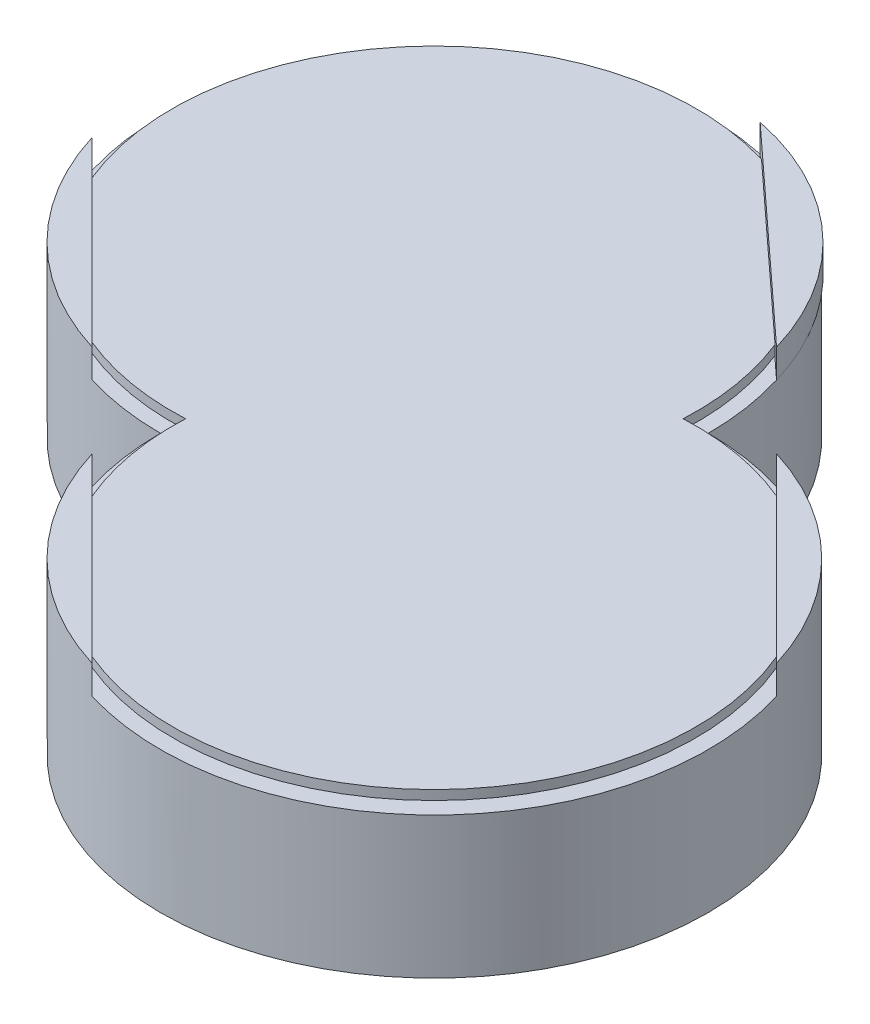
SolidWorks part; units mm, degrees
ref_plane "Front Plane" through (0, 0, 0) normal (0, 0, 1) x (1, 0, 0)
ref_plane "Top Plane" through (0, 0, 0) normal (0, 1, 0) x (1, 0, 0)
ref_plane "Right Plane" through (0, 0, 0) normal (1, 0, 0) x (0, 0, -1)
sketch "Sketch1" plane through (0, 0, 0) normal (0, 1, 0) x (1, 0, 0)
  line L0 (-44.4879, 0) -> (-58.6165, 14.1994)
  line L1 (0, 44.4879) -> (-14.1994, 58.6165)
  arc A0 (-58.6165, 0) -> (0, 58.6165) centre (0, 0) ccw
  arc A1 (0, 58.6165) -> (-58.6165, 0) centre (-58.6165, 58.6165) ccw
  arc A2 (-14.1994, 58.6165) -> (-58.6165, 14.1994) centre (-58.6165, 58.6165) ccw
  arc A3 (-44.4879, 0) -> (0, 44.4879) centre (0, 0) ccw
  circle A4 centre (-58.6165, 58.6165) radius 15.2571
  circle A5 centre (0, 0) radius 16.0823
  point P11 (0, 0)
extrude "Boss-Extrude1" add sketch "Sketch1" along normal blind 24.13 contours A0 A1 A3 L0 A2 L1 | A5 | A4 region at (-98.3061, 0, -98.3061) region at (-58.6165, 0, -58.6165) region at (0, 0, 0)
extrude "Boss-Extrude2" add sketch "Sketch1<5>" against normal blind 6.096 contours A0 A1 A3 L0 A2 L1 | L0 A3 L1 A2 A5 A4 | A5 | A4 region at (-29.4722, 0, -29.4722) region at (-98.3061, 0, -98.3061) region at (-58.6165, 0, -58.6165) region at (0, 0, 0)
sketch "Sketch1<5>" plane through (0, 0, 0) normal (0, 1, 0) x (1, 0, 0) same geometry as "Sketch1"
sketch "Sketch5" plane through (0, 24.13, 0) normal (0, 1, 0) x (1, 0, 0)
  line L0 (-114.6561, 41.4278) -> (-75.8051, 2.5768)
  line L4 (17.1886, 56.0396) -> (56.0396, 17.1886)
  line L5 (-45.9937, 115.7042) -> (-2.5768, 75.8051)
  line L6 (-17.1886, -56.0396) -> (-56.0396, -17.1886)
  arc A0 (-56.0396, -17.1886) -> (-17.1886, -56.0396) centre (0, 0) ccw
  arc A1 (0, 58.6165) -> (-58.6165, 0) centre (-58.6165, 58.6165) ccw construction
  arc A2 (-58.6165, 0) -> (0, 58.6165) centre (0, 0) ccw construction
  arc A3 (-114.6561, 41.4278) -> (-75.8051, 2.5768) centre (-58.6165, 58.6165) ccw
  arc A4 (-45.9937, 115.7042) -> (-2.5768, 75.8051) centre (-57.2131, 59.9236) cw
  arc A5 (17.1886, 56.0396) -> (56.0396, 17.1886) centre (0, 0) cw
  arc A6 (-4.9869, 138.1489) -> (4.8767, 133.1302) centre (-2.5644, 130.7077) cw
  point P21 (4.8385, 133.2448)
extrude "Boss-Extrude3" add sketch "Sketch5" along normal blind 6.096
sketch "Sketch6" plane through (0, 24.13, 0) normal (0, 1, 0) x (1, 0, 0)
  arc A0 (-9.49, 0) -> (0, -9.49) centre (0, 0) ccw
  arc A1 (-48.9966, 58.6165) -> (-58.6165, 68.2363) centre (-58.6165, 58.6165) ccw
  arc A2 (-58.6165, 68.2363) -> (-68.2363, 58.6165) centre (-51.7705, 51.7705) ccw
  arc A3 (-48.9966, 58.6165) -> (-58.6165, 48.9966) centre (-65.3843, 65.3843) cw
  arc A4 (9.49, 0) -> (0, -9.49) centre (-6.9883, 6.9883) cw
  arc A5 (0, 9.49) -> (-9.49, 0) centre (6.8612, -6.8612) ccw
  arc A6 (9.49, 0) -> (0, 9.49) centre (0, 0) ccw
  arc A7 (-68.2363, 58.6165) -> (-58.6165, 48.9966) centre (-58.6165, 58.6165) ccw
extrude "Cut-Extrude2" cut sketch "Sketch6" against normal blind 6.096
sketch "Sketch7" plane through (0, 24.13, 0) normal (0, 1, 0) x (1, 0, 0)
  arc A0 (-55.8305, 2.5854) -> (-2.5854, 55.8305) centre (0, 0) ccw
  arc A1 (-2.5854, 55.8305) -> (-55.8305, 2.5854) centre (-58.6165, 58.6165) ccw
extrude "Boss-Extrude6" add sketch "Sketch7" along normal blind 2.794
extrude "Cut-Extrude3" cut sketch "Sketch7<3>" along normal blind 0.762
sketch "Sketch7<3>" plane through (0, 24.13, 0) normal (0, 1, 0) x (1, 0, 0) same geometry as "Sketch7"
